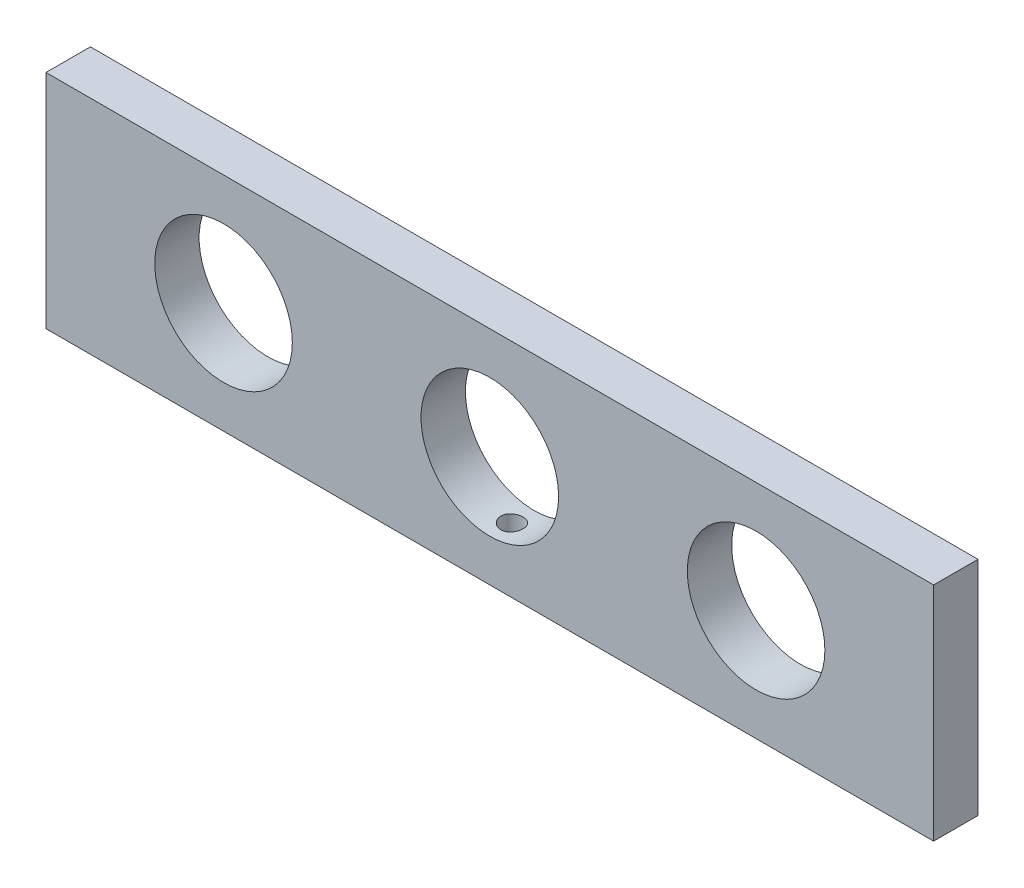
SolidWorks part; units mm, degrees
material "Perspex (TM) GS Acrylic Cast Sheet"
ref_plane "Front Plane" through (0, 0, 0) normal (0, 0, 1) x (1, 0, 0)
ref_plane "Top Plane" through (0, 0, 0) normal (0, 1, 0) x (1, 0, 0)
ref_plane "Right Plane" through (0, 0, 0) normal (1, 0, 0) x (0, 0, -1)
sketch "Sketch1" plane through (0, 0, 0) normal (0, 0, 1) x (1, 0, 0)
  line L1 (-100, 25) -> (100, 25)
  line L2 (-100, 25) -> (-100, -25)
  line L3 (-100, -25) -> (100, -25)
  line L4 (100, 25) -> (100, -25)
  line L5 (-100, 25) -> (100, -25) construction
  line L6 (-100, -25) -> (100, 25) construction
  circle A0 centre (0, 0) radius 15.5
  circle A1 centre (60, 0) radius 15.5
  circle A2 centre (-60, 0) radius 15.5
  point P0 (0, 0)
  dimension "D3" = 31
  dimension "D4" = 60
  dimension "D5" = 60
  dimension "D1" = 200
  dimension "D2" = 50
extrude "Boss-Extrude1" add sketch "Sketch1" along normal blind 10
sketch "Sketch2" plane through (0, -25, 0) normal (0, -1, 0) x (1, 0, 0)
  line L0 (-100, 10) -> (100, 10) construction
  line L1 (-100, 10) -> (-100, 0) construction
  line L2 (100, 10) -> (100, 0) construction
  circle A0 centre (-95, 5) radius 2.5
  circle A1 centre (0, 5) radius 2.5
  circle A2 centre (95, 5) radius 2.5
  dimension "D1" = 5
  dimension "D2" = 5
  dimension "D3" = 5
  dimension "D4" = 5
extrude "Cut-Extrude1" cut sketch "Sketch2" against normal blind 10
